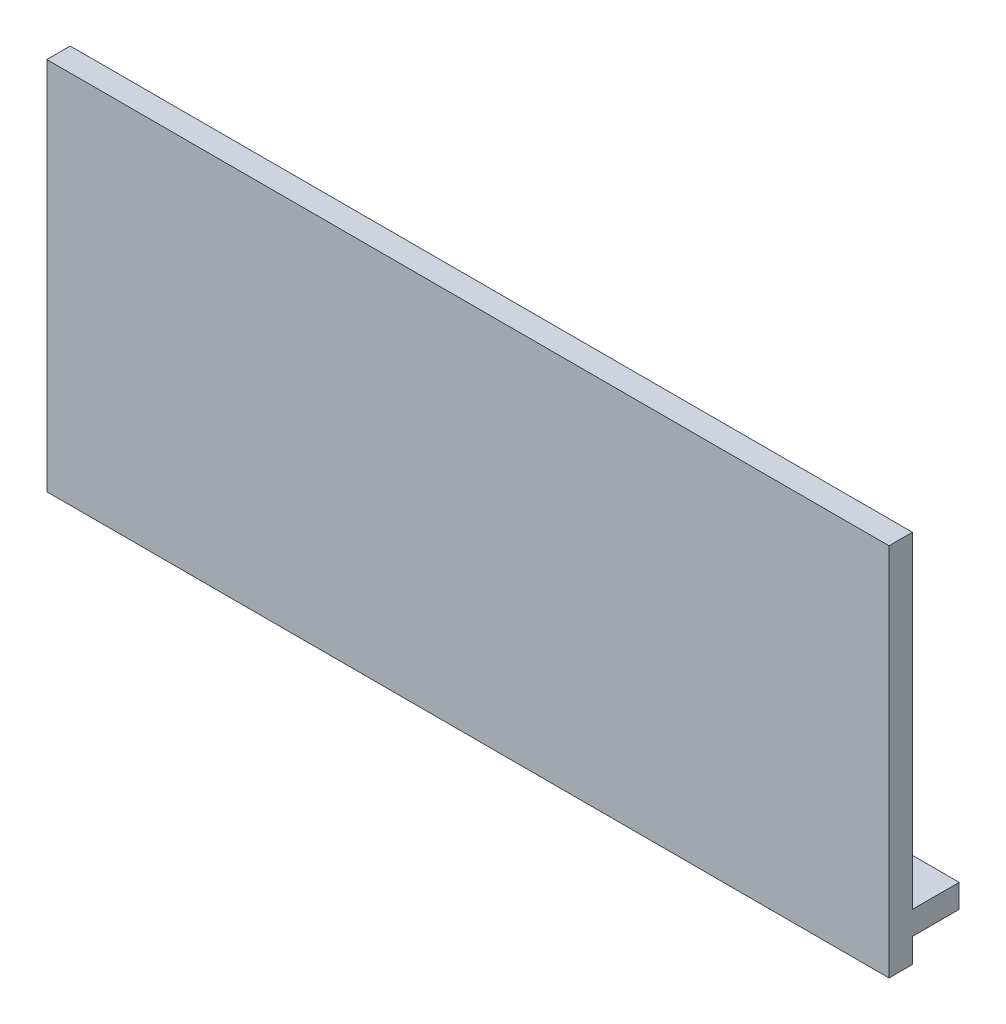
SolidWorks part; units mm, degrees
ref_plane "Front Plane" through (0, 0, 0) normal (0, 0, 1) x (1, 0, 0)
ref_plane "Top Plane" through (0, 0, 0) normal (0, 1, 0) x (1, 0, 0)
ref_plane "Right Plane" through (0, 0, 0) normal (1, 0, 0) x (0, 0, -1)
sketch "Sketch1" plane through (0, 0, 0) normal (0, 0, 1) x (1, 0, 0)
  line L0 (180, 5) -> (180, 0) construction
  line L1 (0, 0) -> (180, 0)
  line L2 (0, 0) -> (0, 80)
  line L3 (0, 80) -> (180, 80)
  line L4 (180, 0) -> (180, 80)
  line L5 (0, 5) -> (180, 5) construction
  line L6 (0, 5) -> (180, 5) construction
  line L7 (0, 5.2) -> (180, 5.2)
  line L8 (0, 10.2) -> (180, 10.2)
  point P16 (0, 0)
  dimension "D1" = 80
  dimension "D2" = 0.2
  dimension "D3" = 5
extrude "Boss-Extrude1" add sketch "Sketch1" along normal blind 5 contours L2 L1 L4 L3
extrude "Boss-Extrude2" add sketch "Sketch1<4>" against normal blind 10 and the other way blind 1 contours L8 L2 L7 L4 region at (90, 7.7, 0)
sketch "Sketch1<4>" plane through (0, 0, 0) normal (0, 0, 1) x (1, 0, 0) same geometry as "Sketch1"
sketch "Sketch2" plane through (0, 10.2, 0) normal (0, 1, 0) x (1, 0, 0)
  line L4 (0, 0) -> (180, 0)
  line L5 (180, 0) -> (180, 10)
  line L6 (180, 10) -> (0, 10)
  line L7 (0, 10) -> (0, 0)
  line L8 (0, 0) -> (180, 0)
  line L9 (180, 0) -> (180, 10)
  line L10 (180, 10) -> (0, 10)
  line L11 (0, 10) -> (0, 0)
  circle A0 centre (15, 5) radius 1.4
  circle A1 centre (90, 5) radius 1.4
  circle A2 centre (165, 5) radius 1.4
  dimension "D2" = 2.8
  dimension "D3" = 2.8
  dimension "D4" = 2.8
  dimension "D1" = 0
extrude "Cut-Extrude3" cut sketch "Sketch2" against normal up to next contours A2 | A1 | A0
equation "\"joit-offset\"= 0.2mm"
equation "\"m3-threaded-hole\"= 2.8mm"
equation "\"m3-passthrow-hole\"= 3.2mm"
